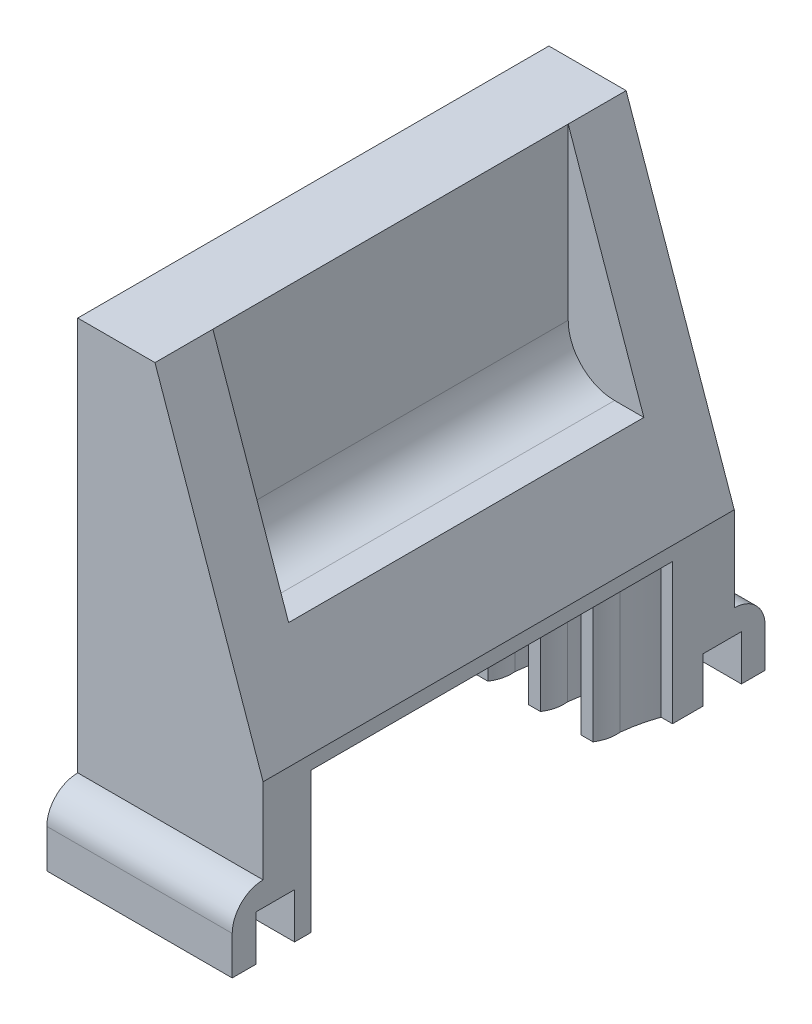
SolidWorks part; units mm, degrees
ref_plane "Front Plane" through (0, 0, 0) normal (0, 0, 1) x (1, 0, 0)
ref_plane "Top Plane" through (0, 0, 0) normal (0, 1, 0) x (1, 0, 0)
ref_plane "Right Plane" through (0, 0, 0) normal (1, 0, 0) x (0, 0, -1)
sketch "Sketch1" plane through (0, 0, 0) normal (0, 0, 1) x (1, 0, 0)
  line L0 (0, 0) -> (0, -30)
  line L1 (0, -30) -> (12, -30)
  line L2 (12, -30) -> (12, -20)
  line L3 (12, -20) -> (5, 0)
  line L4 (5, 0) -> (0, 0)
  dimension "D1" = 30
  dimension "D2" = 12
  dimension "D3" = 10
  dimension "D4" = 5
extrude "Boss-Extrude1" add sketch "Sketch1" against normal blind 30.5
sketch "Sketch4" plane through (0, 0, 0) normal (-1, 0, 0) x (0, 0, 1)
  line L0 (-30.5, 0) -> (-30.5, -30) construction
  line L1 (-26.5, -20.8999) -> (-3.1, -20.8999)
  line L2 (-26.5, -20.8999) -> (-26.5, -30.8999)
  line L3 (-26.5, -30.8999) -> (-3.1, -30.8999)
  line L4 (-3.1, -20.8999) -> (-3.1, -30.8999)
  point P4 (-26.5, -25.8999)
  dimension "D1" = 23.4
  dimension "D2" = 10
  dimension "D3" = 4
extrude "Cut-Extrude2" cut sketch "Sketch4" against normal blind 25 contours L2 L1 L4 L3
ref_plane "Plane1" through (0, 0, -15.25) normal (0, 0, 1) x (1, 0, 0)
sketch "Sketch6" plane through (0, 0, -15.25) normal (0, 0, 1) x (1, 0, 0)
  line L0 (5, 0) -> (5, -14)
  line L1 (5, -14) -> (9.9, -14)
  line L2 (12, -20) -> (5, 0) construction
  line L3 (9.9, -14) -> (5, 0)
  dimension "D1" = 14
extrude "Cut-Extrude4" cut sketch "Sketch6" against normal mid plane 23
ref_plane "Plane2" through (0, -26.4, 0) normal (0, 1, 0) x (1, 0, 0)
ref_plane "Plane3" through (0, -30, 0) normal (0, 1, 0) x (1, 0, 0)
sketch "Sketch7" plane through (0, -30, 0) normal (0, 1, 0) x (1, 0, 0)
  line L0 (11.2768, 28.25) -> (-19.7232, 28.25)
  line L62 (-6.6, 15.25) -> (6.6, 15.25) construction
  line L162 (11.2768, 28.25) -> (11.2768, 26.55)
  line L172 (-19.7232, 26.55) -> (-19.7232, 28.25)
  line L243 (11.2768, 26.55) -> (-19.7232, 26.55)
  dimension "D2" = 31
  dimension "D3" = 1.7
  dimension "D7" = 13
extrude "Boss-Extrude3" add sketch "Sketch7" along normal up to surface (9.1001 mm away) up to face at (6, -20.8999, -14.8)
sketch "Sketch10" plane through (0, -20.8999, 0) normal (0, 1, 0) x (1, 0, 0)
  line L1 (10.0517, 22.9134) -> (10.0517, 23.4692) construction
  line L2 (10.4394, 22.9134) -> (9.664, 22.9134)
  line L4 (-19.7232, 26.55) -> (0, 26.55) construction
  line L5 (8.8265, 26.55) -> (11.2768, 26.55)
  arc A0 (10.4394, 22.9134) -> (10.7757, 24.3322) centre (8.6328, 24.0909) ccw
  arc A1 (10.7757, 24.3322) -> (11.2768, 26.55) centre (20.3354, 23.3375) cw
  arc A2 (9.3277, 24.3322) -> (8.8265, 26.55) centre (-0.232, 23.3375) ccw
  arc A3 (9.664, 22.9134) -> (9.3277, 24.3322) centre (11.4706, 24.0909) cw
  point P15 (8.9473, 26.55)
extrude "Boss-Extrude4" add sketch "Sketch10" against normal up to surface (9.1001 mm away) up to face at (6, -30, -1.55)
pattern_linear "LPattern1" count 9 spacing 3.4 along (-1, 0, 0) of "Boss-Extrude4"
sketch "Sketch11" plane through (0, 0, -30.5) normal (0, 0, -1) x (-1, 0, 0)
  line L0 (-12, -30) -> (-12, -20) construction
  line L1 (-12, -25.5) -> (0, -25.5)
  line L2 (-12, -25.5) -> (-12, -30)
  line L3 (-12, -30) -> (0, -30)
  line L4 (0, -25.5) -> (0, -30)
  dimension "D1" = 4.5
extrude "Boss-Extrude5" add sketch "Sketch11" along normal blind 2
fillet "Fillet1" radius 2 1 edges at (6, -25.5, -32.5)
mirror "Mirror1" about plane through (0, 0, -15.25) normal (0, 0, 1) of "Boss-Extrude5"
fillet "Fillet2" radius 2 1 edges at (6, -25.5, 2)
fillet "Fillet5" radius 3 1 edges at (5, -14, -15.25)
sketch "Sketch12" plane through (0, 0, 0) normal (-1, 0, 0) x (0, 0, 1)
  line L0 (-15.25, -20.6354) -> (-15.25, -36.9741) construction
  line L1 (-30.9639, -27.0644) -> (-28.4639, -27.0644)
  line L2 (-30.9639, -27.0644) -> (-30.9639, -30.5644)
  line L3 (-30.9639, -30.5644) -> (-28.4639, -30.5644)
  line L4 (-28.4639, -27.0644) -> (-28.4639, -30.5644)
  line L11 (-15.25, -16.5) -> (-15.25, 16.5) construction
  line L12 (0.4639, -30.5644) -> (-2.0361, -30.5644)
  line L13 (-2.0361, -27.0644) -> (-2.0361, -30.5644)
  line L14 (0.4639, -27.0644) -> (-2.0361, -27.0644)
  line L15 (0.4639, -27.0644) -> (0.4639, -30.5644)
  dimension "D1" = 2.5
  dimension "D2" = 3.5
extrude "Cut-Extrude5" cut sketch "Sketch12" against normal up to surface (12 mm away) up to face at (12, -25.581, -15.1)
